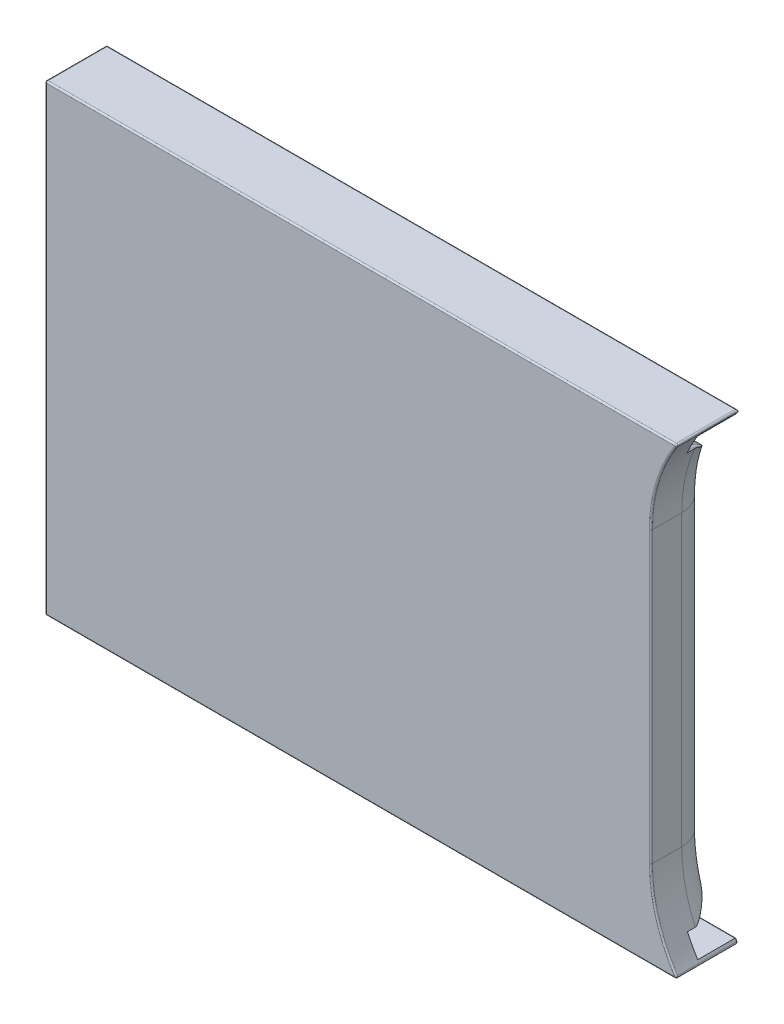
SolidWorks part; units mm, degrees
ref_plane "前视基准面" through (0, 0, 0) normal (0, 0, 1) x (1, 0, 0)
ref_plane "上视基准面" through (0, 0, 0) normal (0, 1, 0) x (1, 0, 0)
ref_plane "右视基准面" through (0, 0, 0) normal (1, 0, 0) x (0, 0, -1)
other "Configuration Table"
sketch "草图1" plane through (0, 0, 0) normal (0, 0, 1) x (1, 0, 0)
  line L1 (0, 0) -> (41, 0)
  line L2 (0, 0) -> (0, 30)
  line L3 (0, 30) -> (41, 30)
  line L4 (41, 0) -> (41, 30)
  dimension "D1" = 41
  dimension "D2" = 30
extrude "凸台-拉伸1" add sketch "草图1" along normal blind 4
sketch "草图2" plane through (0, 0, 0) normal (0, 0, -1) x (-1, 0, 0)
  line L0 (-41, 30) -> (-39.2679, 29)
  line L1 (-39.2679, 29) -> (-39.2679, 1)
  line L2 (-39.2679, 1) -> (-41, 0)
  line L3 (-41, 0) -> (-41, 30)
  line L4 (0, 0) -> (-41, 0) construction
  line L5 (-41, 30) -> (0, 30) construction
  dimension "D1" = 30
  dimension "D2" = 30
  dimension "D3" = 28
extrude "切除-拉伸1" cut sketch "草图2" against normal blind 4
fillet "圆角1" radius 10 2 edges at (39.2679, 1, 2) (39.2679, 29, 2)
sketch "草图3" plane through (0, 0, 0) normal (0, 0, -1) x (-1, 0, 0)
  line L0 (-39.9393, 1.756) -> (-39.9068, 1.7819)
  line L1 (-39.2834, 2) -> (-6, 2)
  line L2 (-5, 3) -> (-5, 27)
  line L3 (-6, 28) -> (-39.2912, 28)
  line L4 (-39.6245, 28.0572) -> (-39.6552, 28.068)
  line L6 (-39.9813, 29.7) -> (0, 29.7)
  line L7 (0, 30) -> (0, 0) construction
  line L8 (0, 29.7) -> (0, 0.3)
  line L9 (0, 0.3) -> (-40.8037, 0.3)
  line L10 (-40.8037, 0.3) -> (-40.1999, 1.4416)
  line L11 (-39.9813, 29.7) -> (-40.8037, 29.7)
  line L12 (-40.8037, 29.7) -> (-40.2102, 28.5517)
  line L13 (-41, 30) -> (0, 30) construction
  line L16 (0, 0) -> (-41, 0) construction
  arc A0 (-41, 0) -> (-39.2679, 5.625) centre (-49.2679, 5.625) ccw construction
  arc A1 (-39.2679, 24.375) -> (-41, 30) centre (-49.2679, 24.375) ccw construction
  arc A2 (-39.2912, 28) -> (-39.6245, 28.0572) centre (-39.2912, 29) cw
  arc A3 (-39.6552, 28.068) -> (-40.2102, 28.5517) centre (-39.3218, 29.0108) cw
  arc A4 (-39.9393, 1.756) -> (-40.1999, 1.4416) centre (-39.3159, 0.9741) ccw
  arc A5 (-39.9068, 1.7819) -> (-39.2834, 2) centre (-39.2834, 1) cw
  arc A6 (-6, 2) -> (-5, 3) centre (-6, 3) ccw
  arc A7 (-5, 27) -> (-6, 28) centre (-6, 27) ccw
  point P25 (-39.4627, 28)
  point P28 (-40.0284, 28.2)
  point P31 (-40.1024, 1.626)
  point P34 (-39.6332, 2)
  dimension "D10" = 1
  dimension "D1" = 2
  dimension "D2" = 2
  dimension "D3" = 0.3
  dimension "D4" = 0.3
  dimension "D5" = 5
  dimension "D6" = 1.5
  dimension "D7" = 0.6
  dimension "D8" = 1.5
  dimension "D9" = 0.6
extrude "切除-拉伸2" cut sketch "草图3" against normal blind 2.5
fillet "圆角4" radius 2 8 edges at (39.4885, 3.5364, 0) (39.2679, 15, 0) (39.4818, 26.4317, 0) (22.6456, 28, 0) (5.2929, 27.7071, 0) (5, 15, 0) (5.2929, 2.2929, 0) (22.6417, 2, 0)
fillet "圆角5" radius 0.1 19 edges at (39.7108, 2.6822, 4) (39.2679, 15, 4) (0, 0.15, 0) (20.5, 0, 0) (40.9005, 0.1491, 0) (20.4018, 0.3, 0) (0, 29.7, 1.25) (0, 15, 4) (0, 0, 2) (0, 15, 2.5) (0, 0.3, 1.25) (0, 30, 2) (20.5, 30, 4) (20.5, 0, 4) (41, 0, 2) (39.7108, 27.3178, 4) (41, 30, 2) (20.5, 30, 0) (20.4018, 29.7, 0)
sketch "草图4" plane through (0, 0, 2.5) normal (0, 0, -1) x (-1, 0, 0)
  line L0 (-4.6, 26.7) -> (-0.1, 26.7)
  line L2 (-0.1, 0.3) -> (-0.1, 29.7) construction
  line L3 (-0.1, 26.7) -> (-0.1, 3.3)
  line L4 (-0.1, 3.3) -> (-4.6, 3.3)
  line L5 (-4.6, 3.3) -> (-4.6, 26.7)
  line L6 (-40.8037, 0.3) -> (-0.1, 0.3) construction
  line L7 (-0.1, 29.7) -> (-40.8037, 29.7) construction
  dimension "D1" = 3
  dimension "D2" = 3
  dimension "D3" = 4.5
extrude "凸台-拉伸2" add sketch "草图4" along normal up to surface (2.5 mm away) up to face at (27.2063, 15, 0)
fillet "圆角6" radius 1 4 edges at (0.1, 15, 0) (2.35, 3.3, 0) (4.6, 15, 0) (2.35, 26.7, 0)
